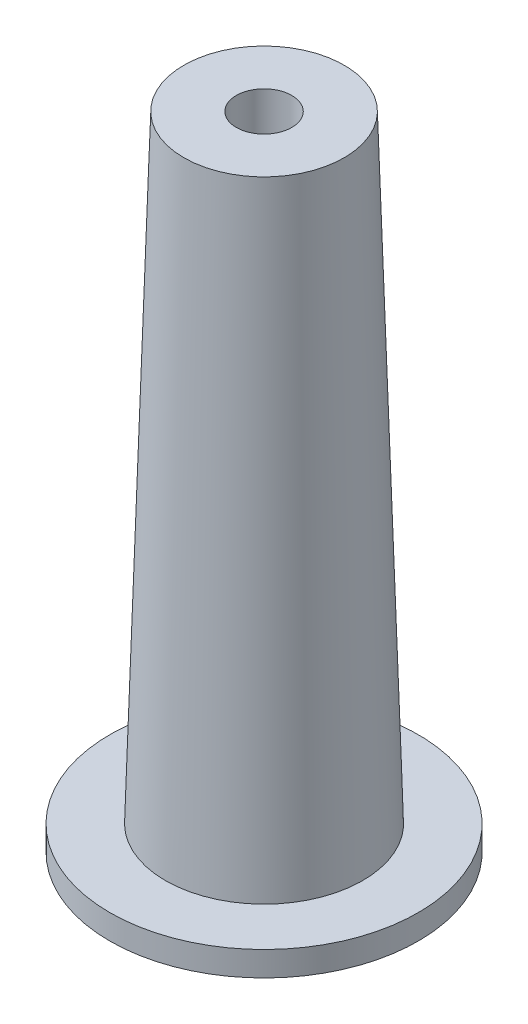
SolidWorks part; units mm, degrees
ref_plane "Front Plane" through (0, 0, 0) normal (0, 0, 1) x (1, 0, 0)
ref_plane "Top Plane" through (0, 0, 0) normal (0, 1, 0) x (1, 0, 0)
ref_plane "Right Plane" through (0, 0, 0) normal (1, 0, 0) x (0, 0, -1)
sketch "Esquisse1" plane through (0, 0, 0) normal (0, 1, 0) x (1, 0, 0)
  circle A0 centre (0, 0) radius 25
extrude "Boss.-Extru.1" add sketch "Esquisse1" along normal blind 4
sketch "Esquisse2" plane through (0, 4, 0) normal (0, 1, 0) x (1, 0, 0)
  circle A0 centre (0, 0) radius 4.5
ref_plane "Plan1" through (0, 0, 0) normal (1, 0, 0) x (0, 0, -1)
ref_axis "Axe1" through (0, 4, 0) along (0, 1, 0)
sketch "Esquisse3" plane through (0, 0, 0) normal (1, 0, 0) x (0, 0, -1)
  line L0 (0, 4) -> (-16, 4)
  line L1 (-16, 4) -> (-13, 104)
  line L2 (-13, 104) -> (0, 104)
  line L3 (0, 104) -> (0, 4)
  dimension "D1" = 100
  dimension "D2" = 13
  dimension "D3" = 16
revolve "Révolution1" add sketch "Esquisse3" angle 360 about L3
extrude "Enlèv. mat.-Extru.1" cut sketch "Esquisse2" against normal blind 1.5 and the other way through all
